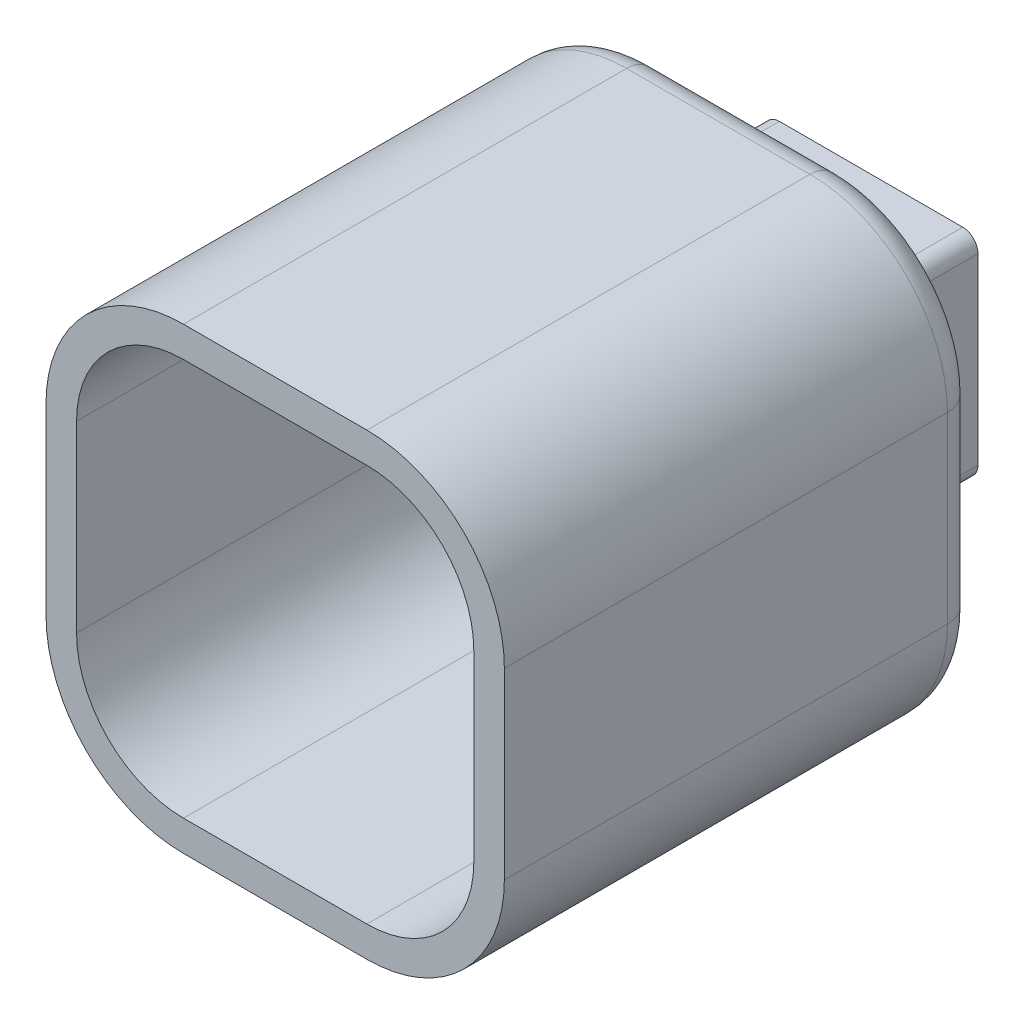
SolidWorks part; units mm, degrees
material "PW20:29:Sc:0:"
ref_plane "Front" through (0, 0, 0) normal (0, 0, 1) x (1, 0, 0)
ref_plane "Top" through (0, 0, 0) normal (0, 1, 0) x (1, 0, 0)
ref_plane "Right" through (0, 0, 0) normal (1, 0, 0) x (0, 0, -1)
sketch "Sketch1" plane through (0, 0, 0) normal (0, 0, 1) x (1, 0, 0)
  line L0 (-11.1125, 11.1125) -> (11.1125, 11.1125)
  line L1 (-11.1125, 11.1125) -> (-11.1125, -11.1125)
  line L2 (11.1125, -11.1125) -> (-11.1125, -11.1125)
  line L3 (11.1125, -11.1125) -> (11.1125, 11.1125)
  line L4 (-11.1125, -11.1125) -> (11.1125, 11.1125) construction
  dimension "D1" = 22.225
extrude "Base-Extrude" add sketch "Sketch1" along normal blind 12.7
fillet "Fillet1" radius 1.5875 4 edges at (11.1125, 11.1125, 6.35) (-11.1125, 11.1125, 6.35) (-11.1125, -11.1125, 6.35) (11.1125, -11.1125, 6.35)
sketch "Sketch2" plane through (0, 0, 12.7) normal (0, 0, 1) x (1, 0, 0)
  line L4 (23.8125, -9.525) -> (23.8125, 9.525)
  line L5 (9.525, 23.8125) -> (-9.525, 23.8125)
  line L6 (-23.8125, 9.525) -> (-23.8125, -9.525)
  line L7 (-9.525, -23.8125) -> (9.525, -23.8125)
  line L8 (23.8125, -9.525) -> (23.8125, 9.525)
  line L9 (9.525, 23.8125) -> (-9.525, 23.8125)
  line L10 (-23.8125, 9.525) -> (-23.8125, -9.525)
  line L11 (-9.525, -23.8125) -> (9.525, -23.8125)
  arc A4 (23.8125, 9.525) -> (9.525, 23.8125) centre (9.525, 9.525) ccw
  arc A5 (-9.525, 23.8125) -> (-23.8125, 9.525) centre (-9.525, 9.525) ccw
  arc A6 (-23.8125, -9.525) -> (-9.525, -23.8125) centre (-9.525, -9.525) ccw
  arc A7 (9.525, -23.8125) -> (23.8125, -9.525) centre (9.525, -9.525) ccw
  arc A8 (23.8125, 9.525) -> (9.525, 23.8125) centre (9.525, 9.525) ccw
  arc A9 (-9.525, 23.8125) -> (-23.8125, 9.525) centre (-9.525, 9.525) ccw
  arc A10 (-23.8125, -9.525) -> (-9.525, -23.8125) centre (-9.525, -9.525) ccw
  arc A11 (9.525, -23.8125) -> (23.8125, -9.525) centre (9.525, -9.525) ccw
  dimension "D1" = 12.7
extrude "Boss-Extrude1" add sketch "Sketch2" along normal blind 49.2125
fillet "Fillet2" radius 3.175 8 edges at (0, -23.8125, 12.7) (19.6278, -19.6278, 12.7) (-19.6278, -19.6278, 12.7) (23.8125, 0, 12.7) (-23.8125, 0, 12.7) (19.6278, 19.6278, 12.7) (-19.6278, 19.6278, 12.7) (0, 23.8125, 12.7)
shell "Shell1" thickness 3.175 removed face at (0, 0, 61.9125) removed face at (0, 0, 0)
fillet "Fillet4" radius 1.5875 4 edges at (-7.9375, 0, 15.875) (0, -7.9375, 15.875) (7.9375, 0, 15.875) (0, 7.9375, 15.875)
